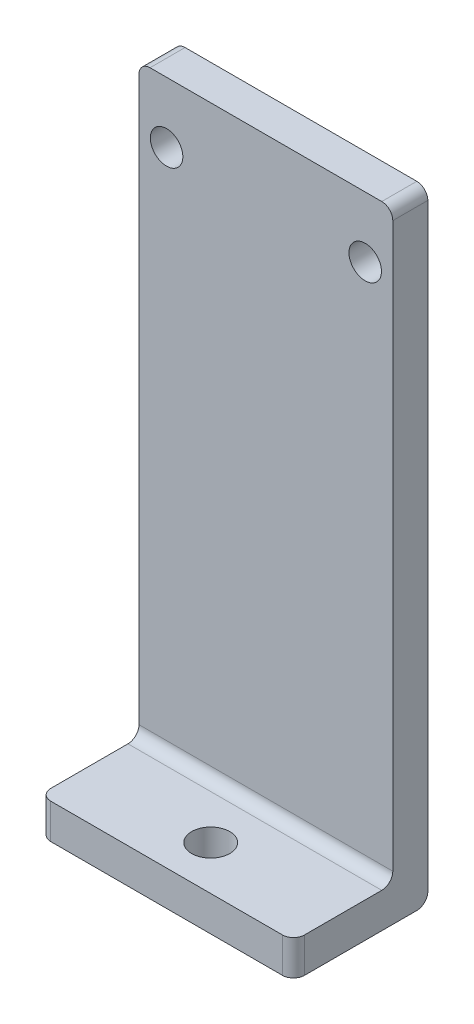
SolidWorks part; units mm, degrees
ref_plane "Front Plane" through (0, 0, 0) normal (0, 0, 1) x (1, 0, 0)
ref_plane "Top Plane" through (0, 0, 0) normal (0, 1, 0) x (1, 0, 0)
ref_plane "Right Plane" through (0, 0, 0) normal (1, 0, 0) x (0, 0, -1)
sketch "Sketch1" plane through (0, 0, 0) normal (0, 0, 1) x (1, 0, 0)
  line L0 (0, -53.06) -> (23, -53.06)
  line L1 (0, 0) -> (23, 0)
  line L2 (0, 0) -> (0, -56.235)
  line L3 (0, -56.235) -> (23, -56.235)
  line L4 (23, 0) -> (23, -56.235)
  circle A0 centre (2.5, -5.5) radius 1.4732
  circle A1 centre (20.5, -5.5) radius 1.4732
  dimension "D2" = 2.9464
  dimension "D1" = 18
  dimension "D4" = 3.175
  dimension "D5" = 23
  dimension "D6" = 2.5
  dimension "D7" = 5.5
  dimension "D3" = 53.06
extrude "Boss-Extrude1" add sketch "Sketch1" along normal blind 3.175 contours L4 L1 L2 L0 A1 A0 | L4 L0 L2 L3 region at (11.5, -26.7676, 0) region at (11.5, -54.6475, 0)
extrude "Boss-Extrude2" add sketch "Sketch1<3>" along normal blind 9 from surface contours L4 L0 L2 L3 region at (11.5, -54.6475, 0) starting at face at (21.9732, -5.5, 3.175)
sketch "Sketch1<3>" plane through (0, 0, 0) normal (0, 0, 1) x (1, 0, 0) same geometry as "Sketch1"
sketch "Mount Hole Location" plane through (0, -53.06, 0) normal (0, 1, 0) x (1, 0, 0)
  line L0 (0, -12.175) -> (23, -12.175) construction
  point P0 (11.5, -8.175)
  point P4 (11.5, -12.175)
  dimension "D1" = 4
hole_wizard "#8-32 Tapped Hole1" positions "3DSketch1" profile "Sketch3" tap size "#8-32" standard "ANSI Inch" end condition through all
sketch3d "3DSketch1"
  point P0 (11.5, -53.06, 8.175)
sketch "Sketch3" plane through (11.5, -53.06, 8.175) normal (1, 0, 0) x (0, 0, 1)
  line L0 (0, 0) -> (0, 3.175)
  line L1 (0, 3.175) -> (1.7272, 3.175)
  line L2 (1.7272, 3.175) -> (1.7272, 0)
  line L5 (1.7272, 0) -> (0, 0)
  line L11 (0, -6.35) -> (0, 107.95) construction
  dimension "Thru Tap Drill Dia." = 3.4544
  dimension "Thru Tap Drill Depth" = 3.175
cosmetic thread "Hole Thread1" parameters "D2"=4.1656
fillet "Fillet1" radius 1 6 edges at (0, -54.6475, 12.175) (23, -54.6475, 12.175) (11.5, -56.235, 0) (0, 0, 1.5875) (23, 0, 1.5875) (11.5, -53.06, 3.175)
equation "\"D6@Sketch1\"=(\"D5@Sketch1\"-\"D1@Sketch1\")/2"
